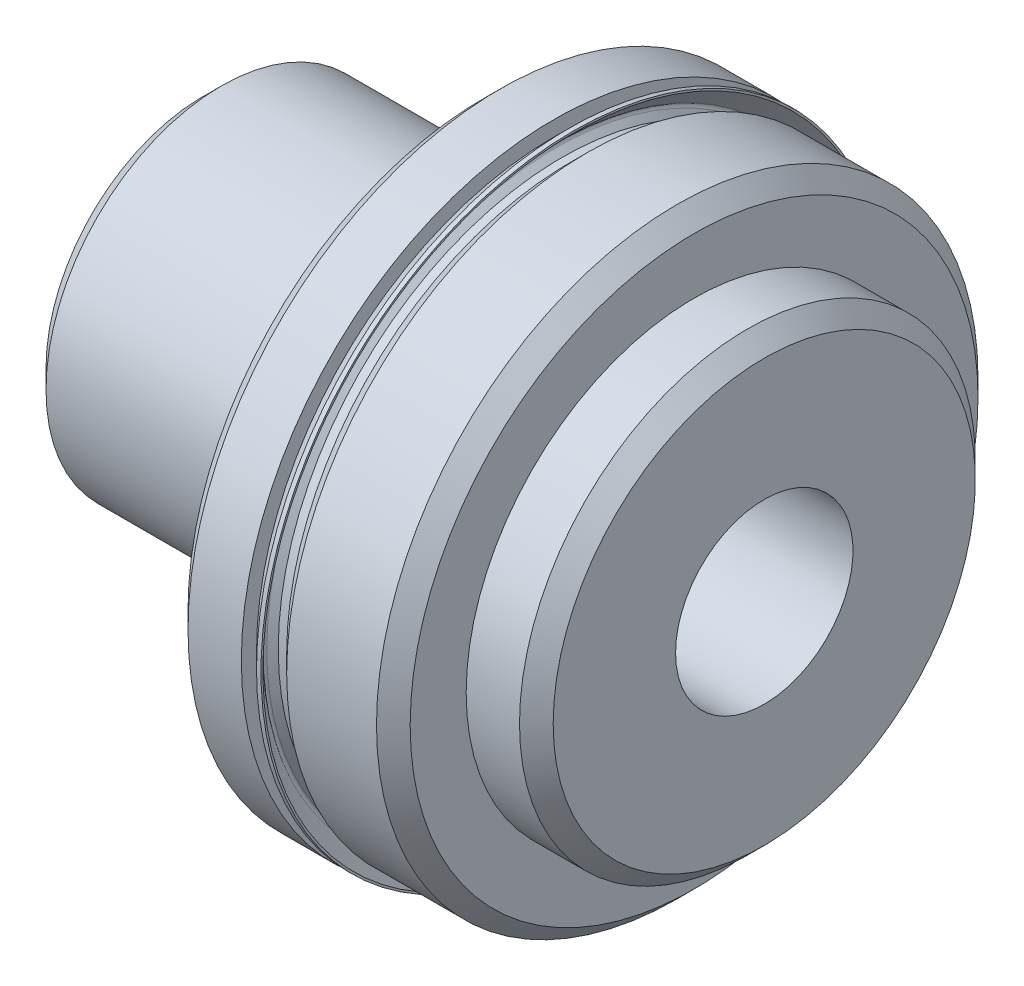
SolidWorks part; units mm, degrees
material "Cast Alloy Steel"
ref_plane "Front Plane" through (0, 0, 0) normal (0, 0, 1) x (1, 0, 0)
ref_plane "Top Plane" through (0, 0, 0) normal (0, 1, 0) x (1, 0, 0)
ref_plane "Right Plane" through (0, 0, 0) normal (1, 0, 0) x (0, 0, -1)
sketch "Sketch1" plane through (0, 0, 0) normal (0, 0, 1) x (1, 0, 0)
  line L0 (0, 0) -> (0, 7.098)
  line L1 (0, 7.098) -> (0.8395, 7.9375)
  line L2 (0.8395, 7.9375) -> (12.7, 7.9375)
  line L3 (12.7, 7.9375) -> (12.7, 0)
  line L4 (12.7, 0) -> (0, 0)
  line L5 (12.7, 0) -> (0, 0) construction
revolve "Revolve1" add sketch "Sketch1" angle 360 about L5 reverse direction yes
cosmetic thread "Cosmetic Thread1" parameters "D1"=12.7, "D2"=14.1961
sketch "Sketch2" plane through (0, 0, 0) normal (0, 0, 1) x (1, 0, 0)
  line L0 (12.7, 0) -> (12.7, 13.3731)
  line L1 (12.7, 13.3731) -> (13.462, 14.1351)
  line L2 (13.462, 14.1351) -> (15.875, 14.1351)
  line L3 (15.875, 14.1351) -> (15.875, 12.846)
  line L4 (15.875, 12.846) -> (16.637, 12.846)
  line L5 (16.637, 12.846) -> (17.399, 13.6081)
  line L6 (17.399, 13.6081) -> (21.463, 13.6081)
  line L7 (21.463, 13.6081) -> (22.225, 12.846)
  line L8 (22.225, 12.846) -> (22.225, 0)
  line L9 (22.225, 0) -> (12.7, 0)
  line L10 (22.225, 0) -> (12.7, 0) construction
revolve "Revolve2" add sketch "Sketch2" angle 360 about L10 reverse direction yes
sketch "Sketch3" plane through (0, 0, 0) normal (0, 0, 1) x (1, 0, 0)
  line L0 (22.225, 0) -> (22.225, 10.3124)
  line L1 (22.225, 10.3124) -> (24.638, 10.3124)
  line L2 (24.638, 10.3124) -> (25.4, 9.5504)
  line L3 (25.4, 9.5504) -> (25.4, 0)
  line L4 (25.4, 0) -> (22.225, 0)
  line L5 (25.4, 0) -> (22.225, 0) construction
revolve "Revolve3" add sketch "Sketch3" angle 360 about L5 reverse direction yes
hole_wizard "Hole1" positions "Sketch5" profile "Sketch4" legacy
sketch "Sketch5" plane through (0, 0, 0) normal (-1, 0, 0) x (0, 0, 1)
  point P0 (0, 0)
sketch "Sketch4" plane through (0, 0, 0) normal (0, 1, 0) x (0, 0, 1)
  line L0 (0, 0) -> (0, 25.4)
  line L1 (0, 25.4) -> (4.0132, 25.4)
  line L2 (4.0132, 25.4) -> (4.0132, 0.762)
  line L3 (4.0132, 0.762) -> (4.7752, 0)
  line L4 (4.7752, 0) -> (0, 0)
  line L5 (0, -6.4453) -> (0, 115.525) construction
  line L6 (-4.0132, 0.762) -> (-4.7752, 0) construction
  dimension "Diameter" = 8.0264
  dimension "Depth" = 25.4
  dimension "C-Sink Angle" = 90
  dimension "C-Sink Diameter" = 9.5504
ref_plane "Plane1" through (18.2626, 0, 0) normal (1, 0, 0) x (0, 0, -1)
ref_plane "Plane2" through (18.2626, 0, 0) normal (1, 0, 0) x (0, 0, -1)
ref_plane "Plane3" through (0, 0, 0) normal (0, -0.7071, 0.7071) x (1, 0, 0)
ref_plane "Plane4" through (2.3368, 0, 0) normal (1, 0, 0) x (0, 0, -1)
ref_plane "Plane5" through (15.875, 0, 0) normal (1, 0, 0) x (0, 0, -1)
ref_plane "Plane6" through (12.7, 0, 0) normal (1, 0, 0) x (0, 0, -1)
ref_plane "Plane7" through (15.875, 0, 0) normal (1, 0, 0) x (0, 0, -1)
sketch "Sketch6" plane through (0, 0, 0) normal (0, 0, 1) x (1, 0, 0)
  line L0 (15.875, 12.5921) -> (16.637, 12.5921)
  line L1 (16.637, 12.5921) -> (16.637, 12.846)
  line L2 (16.637, 12.846) -> (16.256, 12.846)
  line L3 (16.256, 12.846) -> (15.9975, 13.1046)
  line L4 (15.9975, 13.2842) -> (16.7643, 14.0509)
  line L5 (16.7643, 14.0509) -> (16.7643, 14.1351)
  line L6 (16.7643, 14.1351) -> (16.5611, 14.1351)
  line L7 (16.5611, 14.1351) -> (15.875, 13.449)
  line L8 (15.875, 13.449) -> (15.875, 12.5921)
  line L9 (16.637, 0) -> (15.875, 0) construction
  arc A0 (15.9975, 13.1046) -> (15.9975, 13.2842) centre (16.0873, 13.1944) cw
revolve "Revolve4" add sketch "Sketch6" angle 360 about L9 reverse direction yes
ref_plane "Plane8" through (16.637, 0, 0) normal (1, 0, 0) x (0, 0, -1)
ref_plane "Plane9" through (12.7, 0, 0) normal (1, 0, 0) x (0, 0, -1)
ref_plane "Plane10" through (12.7, 0, 0) normal (1, 0, 0) x (0, 0, -1)
ref_plane "Plane11" through (0, 15.875, 0) normal (0, 1, 0) x (1, 0, 0)
ref_plane "Plane12" through (0, -15.875, 0) normal (0, 1, 0) x (1, 0, 0)
ref_plane "Plane13" through (12.7, 0, 0) normal (1, 0, 0) x (0, 0, -1)
ref_plane "Plane14" through (0, 0, 0) normal (0, 1, 0) x (1, 0, 0)
ref_plane "Plane15" through (0, 0, 0) normal (0, 1, 0) x (1, 0, 0)
ref_plane "Plane16" through (0, 10.2743, 0) normal (0, 1, 0) x (1, 0, 0)
ref_plane "Plane17" through (0, 0, 0) normal (1, 0, 0) x (0, 0, -1)
ref_plane "rod_guide XY" through (0, 0, 0) normal (1, 0, 0) x (0, 0, -1)
ref_plane "rod_guide XZ" through (0, 0, 0) normal (0, -1, 0) x (-1, 0, 0)
ref_plane "rod_guide YZ" through (0, 0, 0) normal (0, 0, -1) x (-1, 0, 0)
ref_axis "rod_guide X" through (0, 0, 80.9) along (0, 0, -1)
ref_axis "rod_guide Y" through (0, -50, 0) along (0, 1, 0)
ref_axis "rod_guide Z" through (80.9, 0, 0) along (-1, 0, 0)
sketch3d "rod_guide"
  point P0 (0, 0, 0)
ref_plane "t1 XY" through (12.7, 0, 0) normal (1, 0, 0) x (0, 0, -1)
ref_plane "t1 XZ" through (0, 0, 0) normal (0, -1, 0) x (-1, 0, 0)
ref_plane "t1 YZ" through (0, 0, 0) normal (0, 0, -1) x (-1, 0, 0)
ref_axis "t1 X" through (12.7, 0, 80.9) along (0, 0, -1)
ref_axis "t1 Y" through (12.7, -50, 0) along (0, 1, 0)
ref_axis "t1 Z" through (80.9, 0, 0) along (-1, 0, 0)
sketch3d "t1"
  point P0 (12.7, 0, 0)
ref_plane "t111 XY" through (12.7, 0, 0) normal (1, 0, 0) x (0, 0, -1)
ref_plane "t111 XZ" through (0, 0, 0) normal (0, -1, 0) x (-1, 0, 0)
ref_plane "t111 YZ" through (0, 0, 0) normal (0, 0, -1) x (-1, 0, 0)
ref_axis "t111 X" through (12.7, 0, 80.9) along (0, 0, -1)
ref_axis "t111 Y" through (12.7, -50, 0) along (0, 1, 0)
ref_axis "t111 Z" through (80.9, 0, 0) along (-1, 0, 0)
sketch3d "t111"
  point P0 (12.7, 0, 0)
ref_plane "to_foot_bracket XY" through (12.7, 0, 0) normal (1, 0, 0) x (0, 0, -1)
ref_plane "to_foot_bracket XZ" through (0, 0, 0) normal (0, -1, 0) x (-1, 0, 0)
ref_plane "to_foot_bracket YZ" through (0, 0, 0) normal (0, 0, -1) x (-1, 0, 0)
ref_axis "to_foot_bracket X" through (12.7, 0, 80.9) along (0, 0, -1)
ref_axis "to_foot_bracket Y" through (12.7, -50, 0) along (0, 1, 0)
ref_axis "to_foot_bracket Z" through (80.9, 0, 0) along (-1, 0, 0)
sketch3d "to_foot_bracket"
  point P0 (12.7, 0, 0)
ref_plane "to_nut XY" through (12.7, 0, 0) normal (1, 0, 0) x (0, 0, -1)
ref_plane "to_nut XZ" through (0, 0, 0) normal (0, -1, 0) x (-1, 0, 0)
ref_plane "to_nut YZ" through (0, 0, 0) normal (0, 0, -1) x (-1, 0, 0)
ref_axis "to_nut X" through (12.7, 0, 80.9) along (0, 0, -1)
ref_axis "to_nut Y" through (12.7, -50, 0) along (0, 1, 0)
ref_axis "to_nut Z" through (80.9, 0, 0) along (-1, 0, 0)
sketch3d "to_nut"
  point P0 (12.7, 0, 0)
ref_plane "to_rod XY" through (0, 0, 0) normal (1, 0, 0) x (0, 0, -1)
ref_plane "to_rod XZ" through (0, 0, 0) normal (0, -1, 0) x (-1, 0, 0)
ref_plane "to_rod YZ" through (0, 0, 0) normal (0, 0, -1) x (-1, 0, 0)
ref_axis "to_rod X" through (0, 0, 80.9) along (0, 0, -1)
ref_axis "to_rod Y" through (0, -50, 0) along (0, 1, 0)
ref_axis "to_rod Z" through (80.9, 0, 0) along (-1, 0, 0)
sketch3d "to_rod"
  point P0 (0, 0, 0)
ref_plane "to_screw XY" through (0, 10.2743, 0) normal (0, 1, 0) x (1, 0, 0)
ref_plane "to_screw XZ" through (0, 0, -7.0485) normal (0, 0, 1) x (1, 0, 0)
ref_plane "to_screw YZ" through (11.1252, 0, 0) normal (1, 0, 0) x (0, 0, -1)
ref_axis "to_screw X" through (-80.9, 10.2743, -7.0485) along (1, 0, 0)
ref_axis "to_screw Y" through (11.1252, 10.2743, 50) along (0, 0, -1)
ref_axis "to_screw Z" through (11.1252, 50, -7.0485) along (0, -1, 0)
sketch3d "to_screw"
  point P0 (11.1252, 10.2743, -7.0485)
ref_plane "to_trunnion_brackets XY" through (0, 0, 0) normal (0, 1, 0) x (1, 0, 0)
ref_plane "to_trunnion_brackets XZ" through (0, 0, 0) normal (0, 0, 1) x (1, 0, 0)
ref_plane "to_trunnion_brackets YZ" through (18.2118, 0, 0) normal (1, 0, 0) x (0, 0, -1)
ref_axis "to_trunnion_brackets X" through (-80.9, 0, 0) along (1, 0, 0)
ref_axis "to_trunnion_brackets Y" through (18.2118, 0, 50) along (0, 0, -1)
ref_axis "to_trunnion_brackets Z" through (18.2118, 50, 0) along (0, -1, 0)
sketch3d "to_trunnion_brackets"
  point P0 (18.2118, 0, 0)
ref_plane "to_trunnion_brackets1 XY" through (0, 15.875, 0) normal (0, 1, 0) x (1, 0, 0)
ref_plane "to_trunnion_brackets1 XZ" through (0, 0, 0) normal (0, 0, 1) x (1, 0, 0)
ref_plane "to_trunnion_brackets1 YZ" through (18.2118, 0, 0) normal (1, 0, 0) x (0, 0, -1)
ref_axis "to_trunnion_brackets1 X" through (-80.9, 15.875, 0) along (1, 0, 0)
ref_axis "to_trunnion_brackets1 Y" through (18.2118, 15.875, 50) along (0, 0, -1)
ref_axis "to_trunnion_brackets1 Z" through (18.2118, 50, 0) along (0, -1, 0)
sketch3d "to_trunnion_brackets1"
  point P0 (18.2118, 15.875, 0)
ref_plane "to_trunnion_brackets2 XY" through (0, -15.875, 0) normal (0, 1, 0) x (1, 0, 0)
ref_plane "to_trunnion_brackets2 XZ" through (0, 0, 0) normal (0, 0, 1) x (1, 0, 0)
ref_plane "to_trunnion_brackets2 YZ" through (18.2118, 0, 0) normal (1, 0, 0) x (0, 0, -1)
ref_axis "to_trunnion_brackets2 X" through (-80.9, -15.875, 0) along (1, 0, 0)
ref_axis "to_trunnion_brackets2 Y" through (18.2118, -15.875, 50) along (0, 0, -1)
ref_axis "to_trunnion_brackets2 Z" through (18.2118, 50, 0) along (0, -1, 0)
sketch3d "to_trunnion_brackets2"
  point P0 (18.2118, -15.875, 0)
ref_plane "to_tube XY" through (16.637, 0, 0) normal (1, 0, 0) x (0, 0, -1)
ref_plane "to_tube XZ" through (0, 0, 0) normal (0, -1, 0) x (-1, 0, 0)
ref_plane "to_tube YZ" through (0, 0, 0) normal (0, 0, -1) x (-1, 0, 0)
ref_axis "to_tube X" through (16.637, 0, 80.9) along (0, 0, -1)
ref_axis "to_tube Y" through (16.637, -50, 0) along (0, 1, 0)
ref_axis "to_tube Z" through (80.9, 0, 0) along (-1, 0, 0)
sketch3d "to_tube"
  point P0 (16.637, 0, 0)
